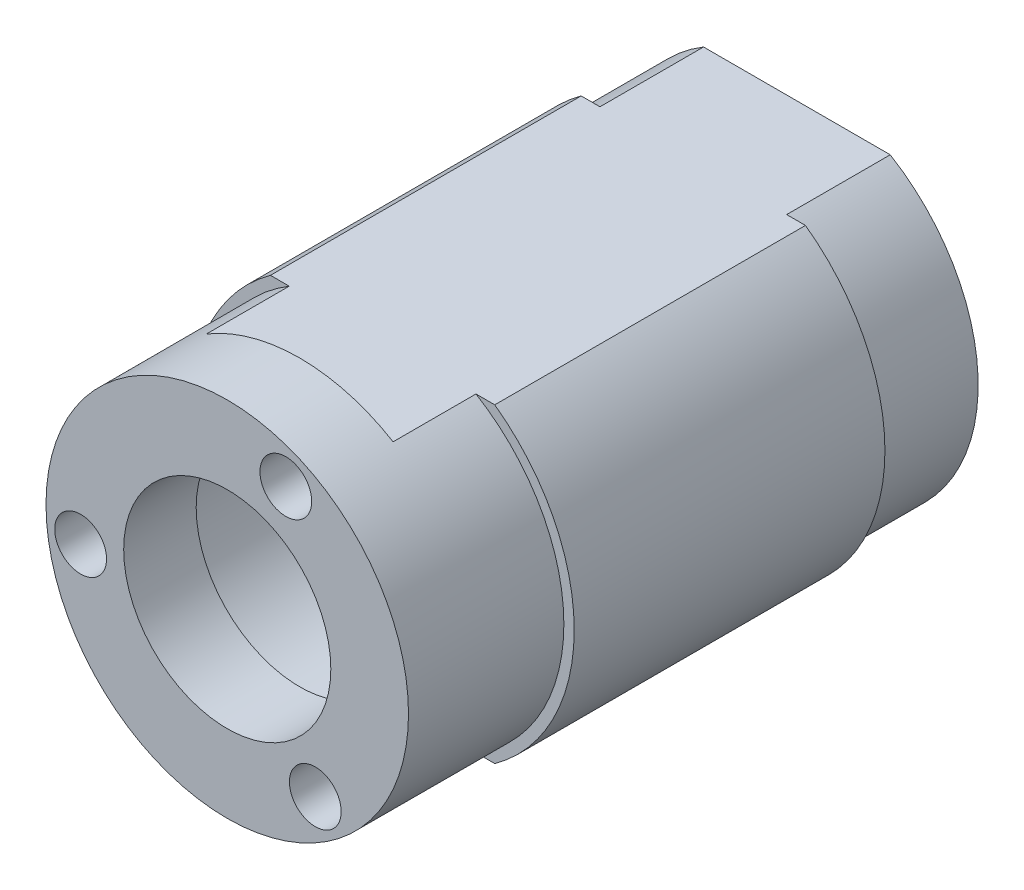
SolidWorks part; units mm, degrees
ref_plane "Front Plane" through (0, 0, 0) normal (0, 0, 1) x (1, 0, 0)
ref_plane "Top Plane" through (0, 0, 0) normal (0, 1, 0) x (1, 0, 0)
ref_plane "Right Plane" through (0, 0, 0) normal (1, 0, 0) x (0, 0, -1)
sketch "Sketch1" plane through (0, 0, 0) normal (0, 0, 1) x (1, 0, 0)
  line L0 (0, 24.7328) -> (0, -23.7417) construction
  line L1 (-10.8282, 15) -> (10.8282, 15)
  line L2 (-10.8282, -15) -> (10.8282, -15)
  circle A0 centre (0, 0) radius 11.5
  circle A1 centre (0, 0) radius 17.5
  circle A2 centre (0, 0) radius 18.5
  point P6 (0, 15)
  point P7 (0, -15)
  dimension "D1" = 15
  dimension "D2" = 37
  dimension "D3" = 35
  dimension "D5" = 15
  dimension "D4" = 23
extrude "Boss-Extrude1" add sketch "Sketch1" along normal blind 30 and the other way blind 25 contours L1 L0 A0 L2 A1 | L0 L1 A1 L2 A0 region at (4.5069, 14.6527, 0) region at (-0.3473, 13.25, 0)
extrude "Boss-Extrude2" add sketch "Sketch1<23>" along normal blind 15 and the other way blind 15 contours L2 A2 L1 A1 | L1 A2 L2 A1 region at (-9.921, 14.6854, 0) region at (16.1906, 8.2807, 0)
sketch "Sketch1<23>" plane through (0, 0, 0) normal (0, 0, 1) x (1, 0, 0) same geometry as "Sketch1"
ref_plane "Plane1" through (0, 0, 30) normal (0, 0, 1) x (1, 0, 0)
sketch "Sketch5" plane through (0, 0, 30) normal (0, 0, 1) x (1, 0, 0)
  line L0 (0, 24.7328) -> (0, -23.7417) construction
  line L1 (-10.8282, 15) -> (10.8282, 15)
  line L2 (-10.8282, -15) -> (10.8282, -15)
  circle A0 centre (0, 0) radius 10
  circle A1 centre (0, 0) radius 17.5
  circle A2 centre (0, 0) radius 18.5
  point P6 (0, 15)
  point P7 (0, -15)
  dimension "D1" = 15
  dimension "D2" = 37
  dimension "D3" = 35
  dimension "D5" = 15
  dimension "D4" = 20
extrude "Boss-Extrude3" add sketch "Sketch5" against normal blind 7 contours L0 L1 A1 L2 A0 | L1 L0 A0 L2 A1 | L0 A1 L1 | A1 L0 L1 | L2 L0 A1 | L0 L2 A1 region at (3.4149, 16.0064, 30) region at (-3.4149, 16.0064, 30) region at (4.5069, 14.6527, 30) region at (-0.3473, 12.5, 30) region at (-3.4149, -16.0064, 30) region at (3.4149, -16.0064, 30)
sketch "Sketch6" plane through (0, 0, 30) normal (0, 0, 1) x (1, 0, 0)
  circle A0 centre (5.6544, 13.0801) radius 2.5
  circle A1 centre (8.5005, -11.4369) radius 2.5
  circle A2 centre (-14.1549, -1.6432) radius 2.5
  point P3 (5.6544, 13.0801)
  point P13 (0, 0)
  dimension "D2" = 5
  dimension "D3" = 3
extrude "Cut-Extrude1" cut sketch "Sketch6" against normal blind 5
ref_plane "Plane2" through (0, 0, -22) normal (0, 0, -1) x (-1, 0, 0)
hole_wizard "M3 Tapped Hole1" positions "Sketch8" profile "Sketch9" tap size "M3" standard "ISO"
sketch "Sketch8" plane through (0, -15, 0) normal (0, -1, 0) x (-1, 0, 0)
  point P0 (0, 0)
sketch "Sketch9" plane through (0, -15, 0) normal (1, 0, 0) x (0, 0, -1)
  line L0 (0, 0) -> (0, 8.2511)
  line L1 (0, 8.2511) -> (1.25, 7.5)
  line L2 (1.25, 7.5) -> (1.25, 0.275)
  line L3 (1.25, 0.275) -> (1.525, 0)
  line L5 (1.525, 0) -> (0, 0)
  line L6 (-1.25, 0.275) -> (-1.525, 0) construction
  line L10 (0, 8.2511) -> (-1.25, 7.5) construction
  line L11 (0, -6.35) -> (0, 107.95) construction
  dimension "Tap Drill Dia." = 2.5
  dimension "Tap Drill Depth" = 7.5
  dimension "Near C'Sink Dia." = 3.05
  dimension "Near C'Sink Angle" = 90
  dimension "Drill Angle" = 118
sketch "Sketch7" plane through (0, 0, -22) normal (0, 0, -1) x (-1, 0, 0)
  circle A0 centre (0, 0) radius 16
  circle A1 centre (0, 0) radius 20
  dimension "D1" = 32
